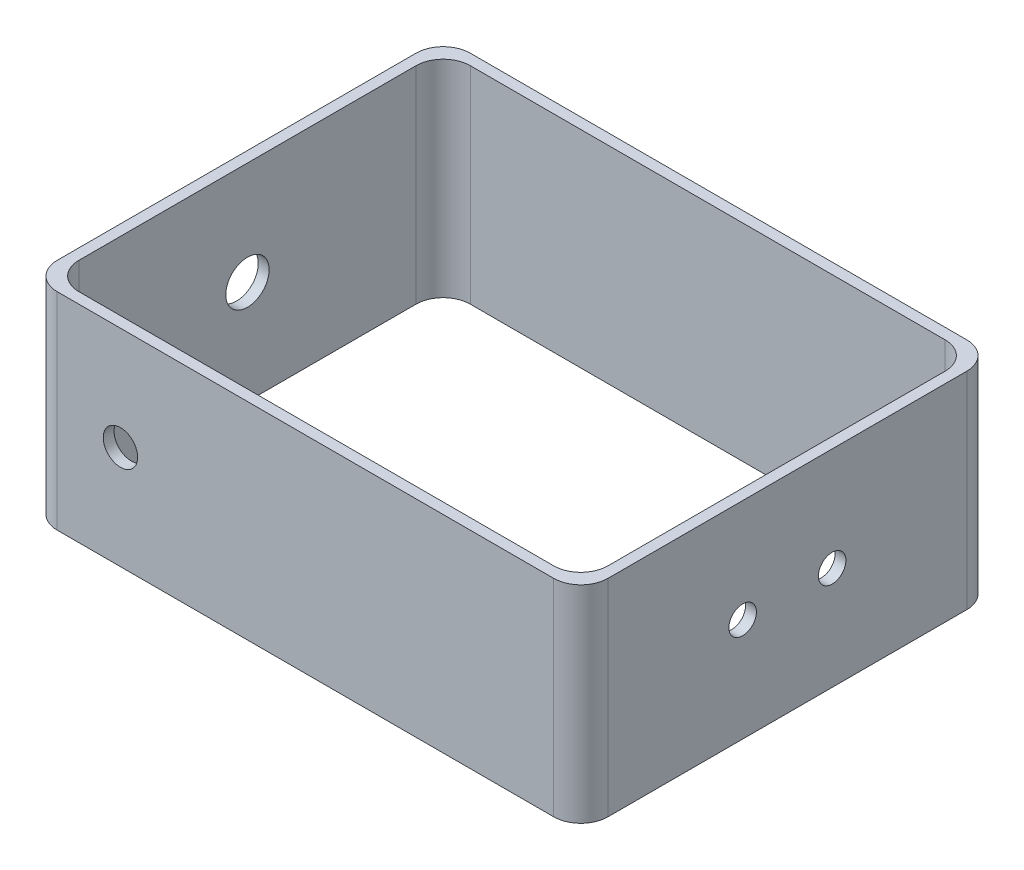
SolidWorks part; units mm, degrees
ref_plane "Front Plane" through (0, 0, 0) normal (0, 0, 1) x (1, 0, 0)
ref_plane "Top Plane" through (0, 0, 0) normal (0, 1, 0) x (1, 0, 0)
ref_plane "Right Plane" through (0, 0, 0) normal (1, 0, 0) x (0, 0, -1)
sketch "Sketch1" plane through (0, 0, 0) normal (0, 1, 0) x (1, 0, 0)
  line L1 (-50.8, 38.1) -> (50.8, 38.1)
  line L2 (-50.8, 38.1) -> (-50.8, -38.1)
  line L3 (-50.8, -38.1) -> (50.8, -38.1)
  line L4 (50.8, 38.1) -> (50.8, -38.1)
  line L5 (-50.8, 38.1) -> (50.8, -38.1) construction
  line L6 (-50.8, -38.1) -> (50.8, 38.1) construction
  point P0 (0, 0)
extrude "Boss-Extrude1" add sketch "Sketch1" along normal blind 38.1
sketch "Sketch3" plane through (0, 38.1, 0) normal (0, 1, 0) x (1, 0, 0)
  line L20 (48.8, -36.1) -> (48.8, 36.1)
  line L21 (-48.8, -36.1) -> (48.8, -36.1)
  line L22 (-48.8, 36.1) -> (-48.8, -36.1)
  line L23 (48.8, 36.1) -> (-48.8, 36.1)
  line L24 (48.8, -36.1) -> (48.8, 36.1)
  line L25 (-48.8, -36.1) -> (48.8, -36.1)
  line L26 (-48.8, 36.1) -> (-48.8, -36.1)
  line L27 (48.8, 36.1) -> (-48.8, 36.1)
  point P0 (0, 0)
  dimension "D1" = 2
extrude "Cut-Extrude1" cut sketch "Sketch3" against normal through all
sketch "Sketch5" plane through (50.8, 0, 0) normal (1, 0, 0) x (0, 0, -1)
  line L0 (0, 0) -> (0, 38.1) construction
  line L1 (-38.1, 0) -> (38.1, 0) construction
  line L2 (-38.1, 38.1) -> (38.1, 38.1) construction
  line L3 (0, 38.1) -> (-38.1, 0) construction
  line L4 (38.1, 0) -> (0, 38.1) construction
  line L5 (0, 0) -> (38.1, 38.1) construction
  line L6 (0, 0) -> (-38.1, 38.1) construction
  point P9 (-19.05, 19.05)
  point P15 (19.05, 19.05)
sketch "Sketch7" plane through (50.8, 0, 0) normal (1, 0, 0) x (0, 0, -1)
  circle A0 centre (-8.255, 19.05) radius 2.54
  circle A1 centre (8.255, 19.05) radius 2.54
extrude "Cut-Extrude2" cut sketch "Sketch7" against normal blind 2
sketch "Sketch9" plane through (-50.8, 0, 0) normal (-1, 0, 0) x (0, 0, 1)
  circle A0 centre (0, 19.05) radius 4
extrude "Cut-Extrude3" cut sketch "Sketch9" against normal blind 2
sketch "Sketch10" plane through (0, 0, 38.1) normal (0, 0, 1) x (1, 0, 0)
  line L0 (-50.8, 19.05) -> (50.8, 19.05) construction
  line L1 (-50.8, 38.1) -> (-50.8, 0) construction
  line L2 (50.8, 38.1) -> (50.8, 0) construction
sketch "Sketch11" plane through (0, 0, 38.1) normal (0, 0, 1) x (1, 0, 0)
  line L0 (-50.8, 19.05) -> (50.8, 19.05) construction
  circle A0 centre (-34.1278, 19.05) radius 3.175
extrude "Cut-Extrude4" cut sketch "Sketch11" against normal blind 2
fillet "Fillet1" radius 5 4 edges at (-50.8, 19.05, 38.1) (-50.8, 19.05, -38.1) (50.8, 19.05, -38.1) (50.8, 19.05, 38.1)
fillet "Fillet2" radius 5 4 edges at (48.8, 19.05, -36.1) (48.8, 19.05, 36.1) (-48.8, 19.05, -36.1) (-48.8, 19.05, 36.1)
sketch "Sketch12" plane through (0, 0, 0) normal (0, -1, 0) x (1, 0, 0)
  text T0 "ΔΣ" font "Century Gothic" height in points 60
extrude "Cut-Extrude5" cut sketch "Sketch12" against normal blind 1 rebuild error yes
